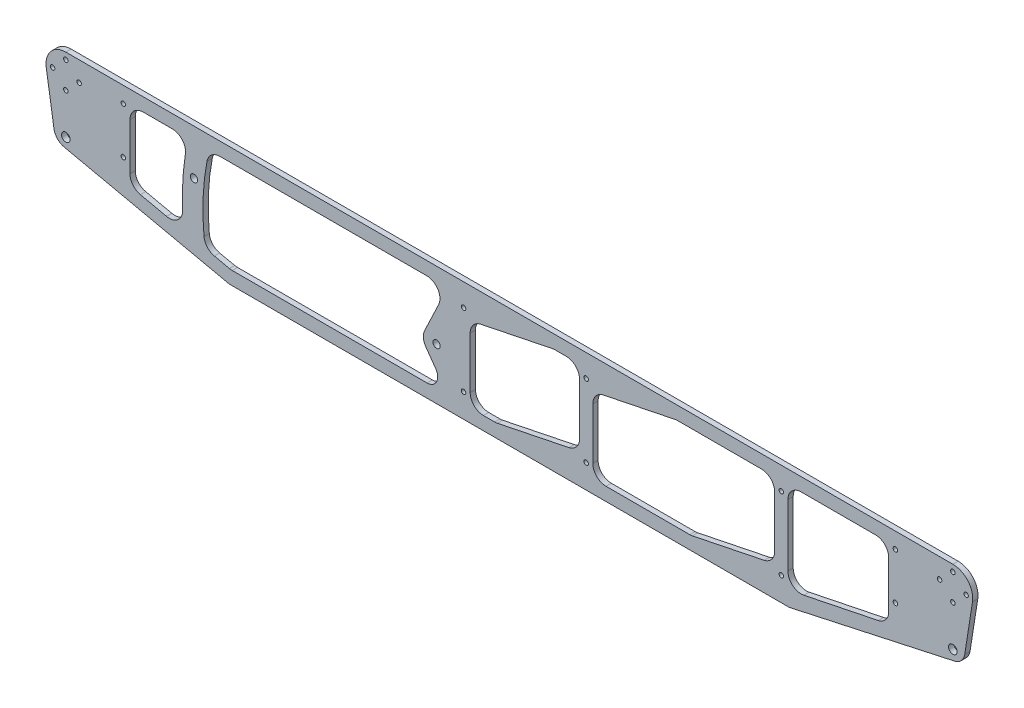
SolidWorks part; units mm, degrees
material "Сплав 2024"
ref_plane "Спереди" through (0, 0, 0) normal (0, 0, 1) x (1, 0, 0)
ref_plane "Сверху" through (0, 0, 0) normal (0, 1, 0) x (1, 0, 0)
ref_plane "Справа" through (0, 0, 0) normal (1, 0, 0) x (0, 0, -1)
sketch "Эскиз1" plane through (0, 0, 0) normal (0, 0, 1) x (1, 0, 0)
  line L0 (-349.8183, 27.6724) -> (-342.9109, -16.3036)
  line L1 (-350, 45) -> (350, 45) construction
  line L2 (-350, 45) -> (-350, -45) construction
  line L3 (-350, -45) -> (350, -45) construction
  line L4 (350, 45) -> (350, -45) construction
  line L5 (-350, 45) -> (350, -45) construction
  line L6 (-350, -45) -> (350, 45) construction
  line L7 (-342.9109, -16.3036) -> (-211.4811, -45)
  line L9 (0, 62.4154) -> (0, -74.3401) construction
  line L10 (-211.4811, -45) -> (211.4811, -45)
  line L12 (-335, 45) -> (335, 45)
  line L15 (342.9109, -16.3036) -> (211.4811, -45)
  line L16 (349.8183, 27.6724) -> (342.9109, -16.3036)
  arc A0 (-335, 45) -> (-349.8183, 27.6724) centre (-335, 30) ccw
  arc A1 (335, 45) -> (349.8183, 27.6724) centre (335, 30) cw
  circle A2 centre (-335, -10.6353) radius 3.25
  circle A3 centre (335, -10.6353) radius 3.25
  point P0 (0, 0)
  point P20 (0, 45)
  point P21 (0, -45)
  dimension "D3" = 30
  dimension "D4" = 6.5
  dimension "D1" = 700
  dimension "D2" = 90
extrude "Бобышка-Вытянуть1" add sketch "Эскиз1" along normal blind 4
sketch "Эскиз2" plane through (0, 0, 4) normal (0, 0, 1) x (1, 0, 0)
  line L0 (0, 49.4785) -> (0, -75.5602) construction
  line L1 (-350, 30) -> (-320, 30) construction
  line L2 (-335, 45) -> (-335, 15) construction
  line L3 (335, 45) -> (335, 15) construction
  line L4 (350, 30) -> (320, 30) construction
  circle A0 centre (-335, 30) radius 15 construction
  arc A1 (-335, 45) -> (-349.8183, 27.6724) centre (-335, 30) ccw construction
  circle A2 centre (-335, 30) radius 10 construction
  circle A4 centre (335, 30) radius 10 construction
  circle A5 centre (335, 30) radius 15 construction
  dimension "D2" = 20
hole_wizard "Отверстие с зазором M32" positions "Эскиз4" profile "Эскиз3" hole size "M3" standard "Ansi Metric" end condition through all
sketch "Эскиз4" plane through (0, 0, 4) normal (0, 0, 1) x (1, 0, 0)
  line L0 (-335, 45) -> (-335, 15) construction
  line L1 (-350, 30) -> (-320, 30) construction
  line L2 (350, 30) -> (320, 30) construction
  line L3 (335, 45) -> (335, 15) construction
  circle A0 centre (-335, 30) radius 10 construction
  circle A1 centre (335, 30) radius 10 construction
  point P0 (-335, 40)
  point P6 (-345, 30)
  point P10 (-335, 20)
  point P12 (-325, 30)
  point P34 (325, 30)
  point P40 (335, 40)
  point P44 (345, 30)
  point P46 (335, 20)
sketch "Эскиз3" plane through (-335, 40, 4) normal (1, 0, 0) x (0, -1, 0)
  line L0 (0, 0) -> (0, 4)
  line L1 (0, 4) -> (1.7, 4)
  line L2 (1.7, 4) -> (1.7, 0)
  line L5 (1.7, 0) -> (0, 0)
  line L11 (0, -6.35) -> (0, 107.95) construction
  dimension "Диаметр сквозного отверстия" = 3.4
  dimension "Глубина сквозного отверстия" = 4
sketch "Эскиз7" plane through (0, 0, 0) normal (0, 0, -1) x (-1, 0, 0)
  line L0 (211.4811, -45) -> (-211.4811, -45) construction
  arc A0 (349.8183, 27.6724) -> (335, 45) centre (335, 30) ccw construction
  point P0 (55, -6)
  point P4 (238.23, 10.84)
  dimension "D1" = 183.23
  dimension "D2" = 16.84
  dimension "D3" = 280
  dimension "D4" = 39
hole_wizard "Отверстие с зазором M52" positions "Эскиз9" profile "Эскиз8" hole size "M5" standard "Ansi Metric" end condition through all
sketch "Эскиз9" plane through (0, 0, 0) normal (0, 0, -1) x (-1, 0, 0)
  point P0 (55, -6)
  point P3 (238.23, 10.84)
sketch "Эскиз8" plane through (-55, -6, 0) normal (1, 0, 0) x (0, 1, 0)
  line L0 (0, 0) -> (0, 4)
  line L1 (0, 4) -> (2.75, 4)
  line L2 (2.75, 4) -> (2.75, 0)
  line L5 (2.75, 0) -> (0, 0)
  line L11 (0, -6.35) -> (0, 107.95) construction
  dimension "Диаметр сквозного отверстия" = 5.5
  dimension "Глубина сквозного отверстия" = 4
sketch "Эскиз10" plane through (0, 0, 4) normal (0, 0, 1) x (1, 0, 0)
  line L0 (-286.5713, 35) -> (-242.5713, 35)
  line L1 (335, 45) -> (-335, 45) construction
  line L2 (-286.5713, 35) -> (-286.5713, -18.3692)
  line L3 (-286.5713, -18.3692) -> (-245.8185, -27.2672)
  line L4 (0, 45) -> (0, -45) construction
  line L5 (-342.9109, -16.3036) -> (-211.4811, -45) construction
  line L6 (-226.6719, 35) -> (-46.5878, 35)
  line L7 (-210.4021, -35) -> (-46.5878, -35)
  line L8 (-211.4811, -45) -> (211.4811, -45) construction
  line L9 (-210.4021, -35) -> (-229.7525, -30.775)
  line L10 (-46.5878, 35) -> (-64.032, -1.7078)
  line L11 (-46.5878, -35) -> (-63.1395, -11.8093)
  line L12 (286.5713, 35) -> (286.5713, -18.3692)
  line L13 (286.5713, -18.3692) -> (210.4021, -34)
  line L14 (286.5713, 35) -> (210.4021, 35)
  line L15 (210.4021, 35) -> (210.4021, -34)
  line L16 (210.4021, -42) -> (210.4021, 43) construction
  line L17 (200.4021, 35) -> (126.1451, 35)
  line L18 (200.4021, -42) -> (200.4021, 43) construction
  line L19 (-29.5979, -42) -> (-29.5979, 43) construction
  line L20 (-29.5979, 22.0494) -> (-29.5979, -35)
  line L21 (-29.5979, -35) -> (-10.0721, -35)
  line L22 (200.4021, -22.0494) -> (200.4021, 35)
  line L23 (53.0365, 35) -> (53.0365, -22.0494)
  line L24 (63.0365, 22.0494) -> (63.0365, -35)
  line L25 (33.5107, 35) -> (-29.5979, 22.0494)
  line L26 (200.4021, -22.0494) -> (137.2934, -35)
  line L28 (63.0365, -35) -> (137.2934, -35)
  line L29 (126.1451, 35) -> (63.0365, 22.0494)
  line L30 (53.0365, -22.0494) -> (-10.0721, -35)
  line L34 (53.0365, 35) -> (33.5107, 35)
  arc A0 (-64.032, -1.7078) -> (-63.1395, -11.8093) centre (-55, -6) ccw
  arc A2 (-242.5713, 35) -> (-245.8185, -27.2672) centre (-55, -6) ccw
  arc A3 (-226.6719, 35) -> (-229.7525, -30.775) centre (-55, -6) ccw
  dimension "D4" = 384
  dimension "D5" = 353
  dimension "D2" = 20
  dimension "D1" = 10
  dimension "D3" = 10
  dimension "D6" = 10
  dimension "D7" = 10
  dimension "D8" = 10
  dimension "D9" = 44
  dimension "D10" = 10
  dimension "D11" = 57.0494
extrude "Вырез-Вытянуть3" cut sketch "Эскиз10" against normal through all
fillet "Скругление2" radius 10 16 edges at (-46.5878, 35, 2) (-210.4021, -35, 2) (-229.7525, -30.775, 2) (-226.6719, 35, 2) (-242.5713, 35, 2) (-245.8185, -27.2672, 2) (-286.5713, -18.3692, 2) (-286.5713, 35, 2) (-342.9109, -16.3036, 2) (-211.4811, -45, 2) (211.4811, -45, 2) (342.9109, -16.3036, 2) (286.5713, 35, 2) (286.5713, -18.3692, 2) (210.4021, 35, 2) (210.4021, -34, 2)
fillet "Скругление3" radius 10 12 edges at (-29.5979, -35, 2) (200.4021, 35, 2) (53.0365, 35, 2) (200.4021, -22.0494, 2) (137.2934, -35, 2) (33.5107, 35, 2) (-29.5979, 22.0494, 2) (63.0365, -35, 2) (126.1451, 35, 2) (63.0365, 22.0494, 2) (53.0365, -22.0494, 2) (-10.0721, -35, 2)
sketch "Эскиз11" plane through (0, 0, 4) normal (0, 0, 1) x (1, 0, 0)
  line L0 (205.4021, 45) -> (205.4021, -45) construction
  line L1 (335, 45) -> (-335, 45) construction
  line L2 (-210.4021, -45) -> (210.4021, -45) construction
  line L3 (200.4021, -13.8931) -> (200.4021, 25) construction
  line L4 (199.8709, -27) -> (211.9144, -27) construction
  line L5 (202.3145, 28) -> (208.249, 28) construction
  line L6 (-34.5979, 45) -> (-34.5979, -45) construction
  line L7 (-29.5979, 13.8931) -> (-29.5979, -25) construction
  line L8 (-39.6608, -27) -> (-30.9685, -27) construction
  line L9 (-37.6326, 28) -> (-30.9685, 28) construction
  line L10 (291.5713, 36.1496) -> (291.5713, -11.5594) construction
  line L11 (286.5713, -10.2129) -> (286.5713, 25) construction
  line L12 (294.823, -2) -> (288.4097, -2) construction
  line L13 (294.823, 33) -> (288.4097, 33) construction
  line L14 (0, 45) -> (0, 71.0849) construction
  line L15 (-294.823, 33) -> (-288.4097, 33) construction
  line L16 (-294.823, -2) -> (-288.4097, -2) construction
  line L17 (-291.5713, 36.1496) -> (-291.5713, -11.5594) construction
  line L18 (58.0365, 45) -> (58.0365, -45) construction
  line L19 (53.0365, -13.8931) -> (53.0365, 25) construction
  line L20 (53.8048, -27) -> (63.1419, -27) construction
  line L21 (64.656, 28) -> (53.8048, 28) construction
  dimension "D1" = 5
  dimension "D2" = 18
  dimension "D3" = 55
  dimension "D4" = 5
  dimension "D5" = 18
  dimension "D6" = 55
  dimension "D7" = 5
  dimension "D8" = 35
  dimension "D9" = 5
  dimension "D10" = 18
  dimension "D11" = 55
hole_wizard "Отверстие с зазором M31" positions "Эскиз13" profile "Эскиз12" hole size "M3" standard "Ansi Metric" end condition through all
sketch "Эскиз13" plane through (0, 0, 4) normal (0, 0, 1) x (1, 0, 0)
  line L0 (-34.5979, 45) -> (-34.5979, -45) construction
  line L1 (-37.6326, 28) -> (-30.9685, 28) construction
  line L2 (-39.6608, -27) -> (-30.9685, -27) construction
  line L3 (205.4021, 45) -> (205.4021, -45) construction
  line L4 (199.8709, -27) -> (211.9144, -27) construction
  line L5 (202.3145, 28) -> (208.249, 28) construction
  line L6 (291.5713, 36.1496) -> (291.5713, -11.5594) construction
  line L7 (294.823, 33) -> (288.4097, 33) construction
  line L8 (294.823, -2) -> (288.4097, -2) construction
  line L9 (-294.823, -2) -> (-288.4097, -2) construction
  line L10 (-294.823, 33) -> (-288.4097, 33) construction
  line L11 (-291.5713, 36.1496) -> (-291.5713, -11.5594) construction
  line L12 (58.0365, 45) -> (58.0365, -45) construction
  line L13 (64.656, 28) -> (53.8048, 28) construction
  line L14 (53.8048, -27) -> (63.1419, -27) construction
  point P0 (-34.5979, 28)
  point P6 (-34.5979, -27)
  point P10 (205.4021, -27)
  point P16 (205.4021, 28)
  point P22 (291.5713, 33)
  point P28 (291.6163, -2)
  point P32 (-291.6163, -2)
  point P36 (-291.5713, 33)
  point P49 (58.0365, 28)
  point P55 (58.0365, -27)
sketch "Эскиз12" plane through (-34.5979, 28, 4) normal (1, 0, 0) x (0, -1, 0)
  line L0 (0, 0) -> (0, 4)
  line L1 (0, 4) -> (1.7, 4)
  line L2 (1.7, 4) -> (1.7, 0)
  line L5 (1.7, 0) -> (0, 0)
  line L11 (0, -6.35) -> (0, 107.95) construction
  dimension "Диаметр сквозного отверстия" = 3.4
  dimension "Глубина сквозного отверстия" = 4
sketch "Эскиз14" plane through (0, 0, 4) normal (0, 0, 1) x (1, 0, 0)
  line L0 (0, 59.2479) -> (0, -65.4566) construction
fillet "Скругление4" radius 8 1 edges at (-46.5878, -35, 2)
sketch "Эскиз15" plane through (0, 0, 0) normal (0, 0, 1) x (1, 0, 0)
  line L0 (-350, 110.1025) -> (-350, -45) construction
  line L1 (-350, -45) -> (-196.6137, -45) construction
  line L2 (-210.4021, -45) -> (210.4021, -45) construction
  line L3 (350, 94.0601) -> (350, -69.6023) construction
  arc A0 (-335, 45) -> (-349.8183, 27.6724) centre (-335, 30) ccw construction
  arc A1 (349.8183, 27.6724) -> (335, 45) centre (335, 30) ccw construction
